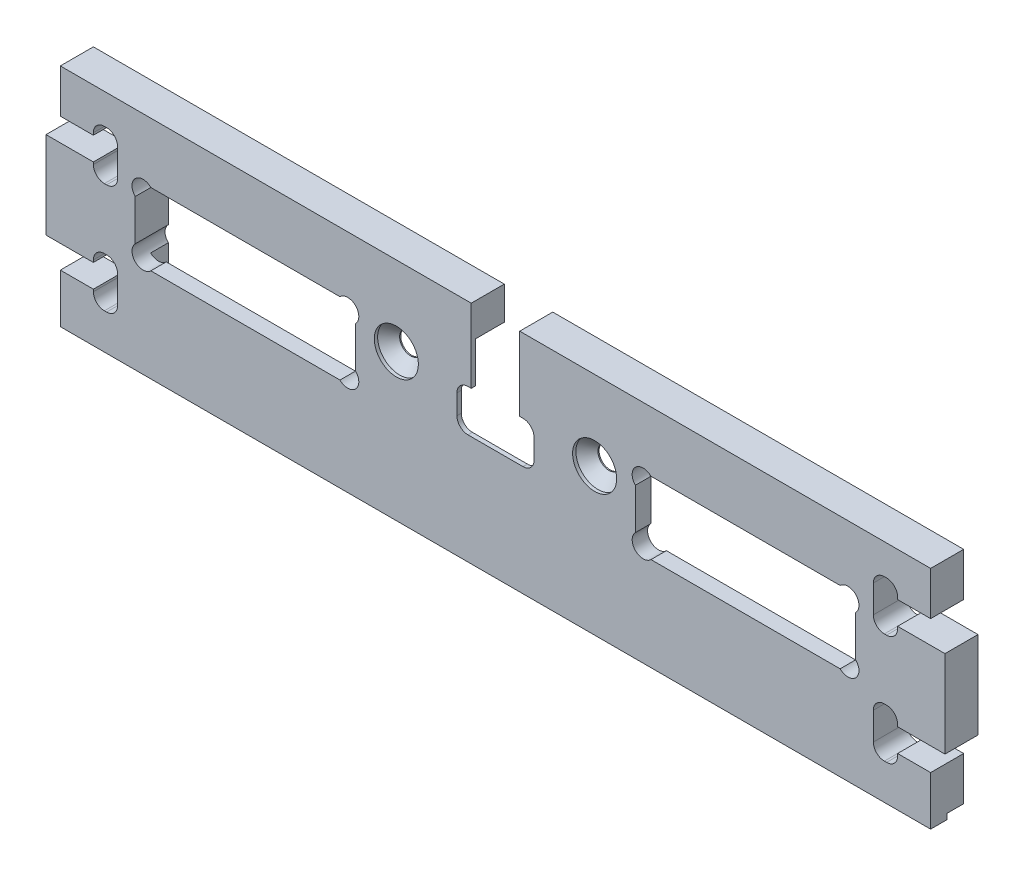
SolidWorks part; units mm, degrees
ref_plane "Front Plane" through (0, 0, 0) normal (0, 0, 1) x (1, 0, 0)
ref_plane "Top Plane" through (0, 0, 0) normal (0, 1, 0) x (1, 0, 0)
ref_plane "Right Plane" through (0, 0, 0) normal (1, 0, 0) x (0, 0, -1)
sketch "Sketch1" plane through (0, 0, 0) normal (0, 0, 1) x (1, 0, 0)
  line L0 (-39.5, 0) -> (39.5, 0) construction
  line L1 (-39.5, 10) -> (39.5, 10)
  line L2 (-39.5, 10) -> (-39.5, -10)
  line L3 (-39.5, -10) -> (39.5, -10)
  line L4 (39.5, 10) -> (39.5, -10)
  line L5 (-39.5, 10) -> (39.5, -10) construction
  line L6 (-39.5, -10) -> (39.5, 10) construction
  line L7 (0, 10) -> (0, -10) construction
  line L9 (-40.8, -3.95) -> (-39.5, -3.95)
  line L10 (-40.8, -3.95) -> (-40.8, 3.95)
  line L11 (-40.8, 3.95) -> (-39.5, 3.95)
  line L12 (-39.5, -3.95) -> (-39.5, 3.95)
  line L13 (-40.8, -3.95) -> (-39.5, 3.95) construction
  line L14 (-40.8, 3.95) -> (-39.5, -3.95) construction
  line L16 (40.8, 3.95) -> (39.5, 3.95)
  line L17 (40.8, -3.95) -> (40.8, 3.95)
  line L18 (40.8, -3.95) -> (39.5, -3.95)
  line L19 (-39.5, 5) -> (39.5, 5) construction
  line L20 (-35.4, 7.25) -> (-35.4, 2.75) construction
  line L21 (-36.5, 3.95) -> (-39.5, 3.95)
  line L22 (-36.5, 3.95) -> (-36.5, 6.05)
  line L23 (-36.5, 6.05) -> (-39.5, 6.05)
  line L24 (-39.5, 3.95) -> (-39.5, 6.05)
  line L25 (-36.5, 3.95) -> (-39.5, 6.05) construction
  line L26 (-36.5, 6.05) -> (-39.5, 3.95) construction
  line L27 (-34.3, 7.25) -> (-36.5, 7.25)
  line L28 (-34.3, 7.25) -> (-34.3, 2.75)
  line L29 (-34.3, 2.75) -> (-36.5, 2.75)
  line L30 (-36.5, 7.25) -> (-36.5, 2.75)
  line L31 (-34.3, 7.25) -> (-36.5, 2.75) construction
  line L32 (-34.3, 2.75) -> (-36.5, 7.25) construction
  line L33 (-34.3, -7.25) -> (-36.5, -7.25)
  line L34 (-34.3, -7.25) -> (-34.3, -2.75)
  line L35 (-34.3, -2.75) -> (-36.5, -2.75)
  line L36 (-36.5, -7.25) -> (-36.5, -2.75)
  line L37 (-36.5, -3.95) -> (-39.5, -3.95)
  line L38 (-36.5, -6.05) -> (-39.5, -6.05)
  line L39 (36.5, 3.95) -> (39.5, 3.95)
  line L40 (36.5, 6.05) -> (39.5, 6.05)
  line L41 (36.5, 7.25) -> (36.5, 2.75)
  line L42 (34.3, 7.25) -> (36.5, 7.25)
  line L43 (34.3, 7.25) -> (34.3, 2.75)
  line L44 (34.3, 2.75) -> (36.5, 2.75)
  line L45 (34.3, -2.75) -> (36.5, -2.75)
  line L46 (34.3, -7.25) -> (34.3, -2.75)
  line L47 (34.3, -7.25) -> (36.5, -7.25)
  line L48 (36.5, -7.25) -> (36.5, -2.75)
  line L49 (36.5, -6.05) -> (39.5, -6.05)
  line L50 (36.5, -3.95) -> (39.5, -3.95)
  point P0 (0, 0)
  point P10 (-40.15, 0)
  point P15 (-38, 5)
  point P35 (-35.4, 5)
  dimension "D1" = 79
  dimension "D2" = 20
  dimension "D4" = 1.3
  dimension "D7" = 5
  dimension "D8" = 2.1
  dimension "D9" = 3
  dimension "D10" = 2.2
  dimension "D11" = 4.5
extrude "Base shape" add sketch "Sketch1" along normal blind 3 contours L4 L1 L2 L3 | L9 L2 L11 L10 | L16 L4 L18 L17 region at (0, 0, 0) region at (-40.15, 0, 0) region at (40.15, 0, 0)
sketch "Sketch4" plane through (0, -10, 0) normal (0, -1, 0) x (1, 0, 0)
  line L0 (39.5, 3) -> (39.5, 0) construction
  line L1 (-39.5, 3) -> (39.5, 3)
  line L2 (-39.5, 3) -> (-39.5, 1.5)
  line L3 (-39.5, 1.5) -> (39.5, 1.5)
  line L4 (39.5, 3) -> (39.5, 1.5)
extrude "Floor lip" add sketch "Sketch4" along normal blind 0.5
sketch "Sketch6" plane through (0, 0, 0) normal (0, 0, -1) x (-1, 0, 0)
  line L0 (0, 0) -> (0, -10) construction
  line L1 (39.5, -10) -> (-39.5, -10) construction
  line L2 (-4, -10) -> (4, -10) construction
  line L3 (39.5, -10) -> (-39.5, -10) construction
  line L4 (-4, -9) -> (4, -9)
  line L5 (-4, -11) -> (4, -11)
  arc A0 (-4, -9) -> (-4, -11) centre (-4, -10) ccw
  arc A1 (4, -11) -> (4, -9) centre (4, -10) ccw
  point P9 (0, -10)
  dimension "D1" = 2
  dimension "D2" = 8
extrude "Nail cutout" cut sketch "Sketch6" against normal up to surface (1.5 mm away) up to face at (0, -10.25, 1.5)
sketch "Sketch3" plane through (-40.8, 0, 0) normal (-1, 0, 0) x (0, 0, 1)
  line L0 (0, 6.05) -> (3, 3.95) construction
  line L1 (0, 6.05) -> (3, 6.05)
  line L2 (0, 6.05) -> (0, 3.95)
  line L3 (0, 3.95) -> (3, 3.95)
  line L4 (3, 6.05) -> (3, 3.95)
  line L5 (0, -3.95) -> (3, -6.05) construction
  line L6 (0, -3.95) -> (3, -3.95)
  line L7 (0, -3.95) -> (0, -6.05)
  line L8 (0, -6.05) -> (3, -6.05)
  line L9 (3, -3.95) -> (3, -6.05)
  point P6 (1.5, 5)
  point P13 (1.5, -5)
ref_axis "Tap axis top" through (-53.7846, 5, 1.5) along (1, 0, 0)
ref_axis "Tap axis bottom" through (-54.2844, -5, 1.5) along (1, 0, 0)
fillet "Mill fillets" radius 1 16 edges at (36.5, -7.25, 1.5) (36.5, 2.75, 1.5) (34.3, 2.75, 1.5) (34.3, -7.25, 1.5) (36.5, -2.75, 1.5) (36.5, 7.25, 1.5) (34.3, -2.75, 1.5) (34.3, 7.25, 1.5) (-36.5, -2.75, 1.5) (-34.3, -2.75, 1.5) (-34.3, -7.25, 1.5) (-36.5, -7.25, 1.5) (-36.5, 2.75, 1.5) (-34.3, 2.75, 1.5) (-34.3, 7.25, 1.5) (-36.5, 7.25, 1.5)
sketch "Sketch8" [suppressed] plane through (0, 0, 3) normal (0, 0, 1) x (1, 0, 0)
  line L0 (-40.8, 0) -> (40.8, 0) construction
  line L1 (-40.8, -3.95) -> (-40.8, 3.95) construction
  line L2 (40.8, -3.95) -> (40.8, 3.95) construction
  line L4 (-24.5, 5.15) -> (24.5, 5.15)
  line L5 (-25.5, 4.15) -> (-25.5, -4.15)
  line L6 (-24.5, -5.15) -> (24.5, -5.15)
  line L7 (25.5, 4.15) -> (25.5, -4.15)
  line L8 (-25.5, 5.15) -> (25.5, -5.15) construction
  line L9 (-25.5, -5.15) -> (25.5, 5.15) construction
  arc A0 (24.5, -5.15) -> (25.5, -4.15) centre (24.5, -4.15) ccw
  arc A1 (24.5, 5.15) -> (25.5, 4.15) centre (24.5, 4.15) cw
  arc A2 (-25.5, -4.15) -> (-24.5, -5.15) centre (-24.5, -4.15) ccw
  arc A3 (-24.5, 5.15) -> (-25.5, 4.15) centre (-24.5, 4.15) ccw
  point P6 (0, 0)
  dimension "D3" = 1
  dimension "D1" = 51
  dimension "D2" = 10.3
extrude "Led strip pocket" [suppressed] cut sketch "Sketch8" against normal offset from surface (2.5 mm away) 0.5 up to face at (0, -0.6712, 0)
sketch "Sketch9" [suppressed] plane through (0, 0, 0.5) normal (0, 0, 1) x (1, 0, 0)
  line L0 (-19.5, 5.15) -> (-19.5, -5.15)
  line L1 (0, 5.15) -> (0, -5.15) construction
  line L2 (19.5, 5.15) -> (19.5, -5.15)
  line L3 (-25.5, -2.978) -> (25.5, -2.978) construction
  line L4 (25.5, -4.15) -> (25.5, 4.15)
  line L5 (24.5, 5.15) -> (-24.5, 5.15)
  line L6 (-25.5, 4.15) -> (-25.5, -4.15)
  line L7 (-24.5, -5.15) -> (24.5, -5.15)
  line L8 (25.5, -4.15) -> (25.5, 4.15)
  line L9 (24.5, 5.15) -> (-24.5, 5.15)
  line L10 (-25.5, 4.15) -> (-25.5, -4.15)
  line L11 (-24.5, -5.15) -> (24.5, -5.15)
  circle A0 centre (-12.7, -2.978) radius 1
  circle A1 centre (12.7, -2.978) radius 1
  arc A4 (24.5, -5.15) -> (25.5, -4.15) centre (24.5, -4.15) ccw
  arc A5 (25.5, 4.15) -> (24.5, 5.15) centre (24.5, 4.15) ccw
  arc A6 (-24.5, 5.15) -> (-25.5, 4.15) centre (-24.5, 4.15) ccw
  arc A7 (-25.5, -4.15) -> (-24.5, -5.15) centre (-24.5, -4.15) ccw
  arc A8 (24.5, -5.15) -> (25.5, -4.15) centre (24.5, -4.15) ccw
  arc A9 (25.5, 4.15) -> (24.5, 5.15) centre (24.5, 4.15) ccw
  arc A10 (-24.5, 5.15) -> (-25.5, 4.15) centre (-24.5, 4.15) ccw
  arc A11 (-25.5, -4.15) -> (-24.5, -5.15) centre (-24.5, -4.15) ccw
  arc M13 (24.5, -5.15) -> (25.5, -4.15) centre (24.5, -4.15) ccw
  line M14 (25.5, -4.15) -> (25.5, 4.15)
  arc M15 (25.5, 4.15) -> (24.5, 5.15) centre (24.5, 4.15) ccw
  line M16 (24.5, 5.15) -> (-24.5, 5.15)
  arc M17 (-24.5, 5.15) -> (-25.5, 4.15) centre (-24.5, 4.15) ccw
  line M18 (-25.5, 4.15) -> (-25.5, -4.15)
  arc M19 (-25.5, -4.15) -> (-24.5, -5.15) centre (-24.5, -4.15) ccw
  line M20 (-24.5, -5.15) -> (24.5, -5.15)
  dimension "D4" = 2
  dimension "D2" = 6
  dimension "D3" = 8.128
  dimension "D5" = 25.4
  dimension "D1" = 0
extrude "Led strip cuts" [suppressed] cut sketch "Sketch9" against normal up to next contours L0 M16 M17 M18 M19 M20 | L2 M16 M20 M13 M14 M15 | A0 | A1
fillet "Led strip cut fillets" [suppressed] radius 1
sketch "Sketch13" plane through (0, 0, 0) normal (0, 0, -1) x (-1, 0, 0)
  line L0 (0, 15.8648) -> (0, -21.9195) construction
  line L2 (-4.2, -6.3) -> (4.2, -6.3)
  line L3 (-5.2, -5.3) -> (-5.2, 6)
  line L4 (-4.2, 7) -> (4.2, 7)
  line L5 (5.2, -5.3) -> (5.2, 6)
  line L6 (-5.2, -6.3) -> (5.2, 7) construction
  line L7 (-5.2, 7) -> (5.2, -6.3) construction
  line L10 (39.5, 10) -> (-39.5, 10) construction
  arc A0 (-4.2, -6.3) -> (-5.2, -5.3) centre (-4.2, -5.3) cw
  arc A1 (4.2, -6.3) -> (5.2, -5.3) centre (4.2, -5.3) ccw
  arc A4 (5.2, 6) -> (4.2, 7) centre (4.2, 6) ccw
  arc A5 (-5.2, 6) -> (-4.2, 7) centre (-4.2, 6) cw
  point P1 (0, 0.35)
  dimension "D4" = 1
  dimension "D5" = 1
  dimension "D1" = 10.4
  dimension "D2" = 13.3
  dimension "D3" = 3
extrude "Bumper mount inner cut" cut sketch "Sketch13" against normal offset from surface (2.6 mm away) 0.4 up to face at (0, -0.0192, 3)
sketch "Sketch14" plane through (0, 0, 0) normal (0, 0, -1) x (-1, 0, 0)
  line L1 (0, 12.9528) -> (0, -14.0841) construction
  line L2 (4.2, 7) -> (-4.2, 7) construction
  line L3 (-4.2, -6.3) -> (4.2, -6.3) construction
  line L4 (-11.7, 7) -> (11.7, 7)
  line L5 (-12.7, 6) -> (-12.7, -5.3)
  line L6 (-11.7, -6.3) -> (11.7, -6.3)
  line L7 (12.7, 6) -> (12.7, -5.3)
  line L8 (-12.7, 7) -> (12.7, -6.3) construction
  line L9 (-12.7, -6.3) -> (12.7, 7) construction
  arc A1 (11.7, -6.3) -> (12.7, -5.3) centre (11.7, -5.3) ccw
  arc A2 (-12.7, -5.3) -> (-11.7, -6.3) centre (-11.7, -5.3) ccw
  arc A3 (11.7, 7) -> (12.7, 6) centre (11.7, 6) cw
  arc A4 (-12.7, 6) -> (-11.7, 7) centre (-11.7, 6) cw
  point P6 (0, 0.35)
  dimension "D2" = 1
  dimension "D3" = 1
  dimension "D1" = 25.4
extrude "Bumper mount outer cut" cut sketch "Sketch14" against normal blind 1.6
sketch "Sketch15" plane through (0, 0, 1.6) normal (0, 0, -1) x (-1, 0, 0)
  line L0 (-12.7, 2.8) -> (12.7, 2.8) construction
  line L3 (0, 16.4744) -> (0, -20.0474) construction
  line L7 (-12.7, 6) -> (-12.7, -5.3) construction
  line L8 (12.7, -5.3) -> (12.7, 6) construction
  line L11 (-4.2, 7) -> (-11.7, 7) construction
  circle A0 centre (-9, 2.8) radius 1
  circle A1 centre (9, 2.8) radius 1
  dimension "D1" = 18
  dimension "D2" = 2
  dimension "D3" = 4.2
extrude "Bumper mount screw holes" cut sketch "Sketch15" against normal up to next
sketch "Sketch16" plane through (0, 0, 2.6) normal (0, 0, -1) x (-1, 0, 0)
  line L0 (-5.2, 1.4) -> (5.2, 1.4) construction
  line L3 (0, 7) -> (0, -4.2) construction
  line L4 (-2.5, 3.3) -> (2.5, 3.3)
  line L5 (-3.5, 2.3) -> (-3.5, 0.5)
  line L6 (-2.5, -0.5) -> (2.5, -0.5)
  line L7 (3.5, 2.3) -> (3.5, 0.5)
  line L8 (-3.5, 3.3) -> (3.5, -0.5) construction
  line L9 (-3.5, -0.5) -> (3.5, 3.3) construction
  line L11 (-5.2, 6) -> (-5.2, -5.3) construction
  line L13 (4.2, 7) -> (-4.2, 7) construction
  arc A0 (2.5, -0.5) -> (3.5, 0.5) centre (2.5, 0.5) ccw
  arc A1 (-3.5, 0.5) -> (-2.5, -0.5) centre (-2.5, 0.5) ccw
  arc A2 (-2.5, 3.3) -> (-3.5, 2.3) centre (-2.5, 2.3) ccw
  arc A3 (2.5, 3.3) -> (3.5, 2.3) centre (2.5, 2.3) cw
  point P6 (0, 1.4)
  dimension "D3" = 1
  dimension "D1" = 7
  dimension "D2" = 3.8
  dimension "D4" = 11.2
extrude "Bumper body cut" cut sketch "Sketch16" against normal up to next
hole_wizard "Bumper screw countersunks" positions "Sketch17" profile "Sketch18" countersink size "M2" standard "ANSI Metric" end condition through all
sketch "Sketch17" plane through (0, 0, 3) normal (0, 0, 1) x (1, 0, 0)
  point P0 (9, 2.8)
  point P3 (-9, 2.8)
sketch "Sketch18" plane through (9, 2.8, 3) normal (1, 0, 0) x (0, -1, 0)
  line L0 (0, 0) -> (0, 3)
  line L1 (0, 3) -> (1, 3)
  line L2 (1, 3) -> (1, 1.3)
  line L3 (1, 1.3) -> (2, 0.3)
  line L4 (2, 0.3) -> (2, 0)
  line L6 (2, 0) -> (0, 0)
  line L7 (-1, 1.3) -> (-2, 0.3) construction
  line L11 (0, -6.35) -> (0, 107.95) construction
  dimension "Thru Hole Dia." = 2
  dimension "Thru Hole Depth" = 3
  dimension "C'Sink Dia." = 4
  dimension "C'Sink Angle" = 90
  dimension "Head Clearance" = 0.3
sketch "Sketch19" plane through (0, 0, 0) normal (0, 0, -1) x (-1, 0, 0)
  line L0 (0, 15.6498) -> (0, -12.9575) construction
  line L1 (39.5, 10) -> (-39.5, 10) construction
  line L2 (-2.2, 3.3) -> (2.2, 3.3)
  line L3 (-2.2, 3.3) -> (-2.2, 10)
  line L4 (-2.2, 10) -> (2.2, 10)
  line L5 (2.2, 3.3) -> (2.2, 10)
  line L6 (-2.2, 3.3) -> (2.2, 10) construction
  line L7 (-2.2, 10) -> (2.2, 3.3) construction
  line L8 (2.5, 3.3) -> (-2.5, 3.3) construction
  point P1 (0, 6.65)
  dimension "D1" = 4.4
extrude "Bumper insertion cut" cut sketch "Sketch19" against normal up to next
sketch "Sketch20" plane through (0, 0, 0) normal (0, 0, -1) x (-1, 0, 0)
  line L0 (-12.7, 6) -> (-12.7, -5.3) construction
  line L1 (-12.7, 4.55) -> (-32.7, 4.55)
  line L2 (-12.7, 4.55) -> (-12.7, -2)
  line L3 (-12.7, -2) -> (-32.7, -2)
  line L4 (-32.7, 4.55) -> (-32.7, -2)
  line L5 (-2.2, 10) -> (-39.5, 10) construction
  line L6 (-12.7, 4.55) -> (-19.25, -2) construction
  line L7 (-22.7, 4.55) -> (-22.7, -2) construction
  line L8 (-32.7, 1.275) -> (-12.7, 1.275) construction
  line L9 (0, 16.176) -> (0, -15.99) construction
  line L10 (12.7, 4.55) -> (12.7, -2)
  line L11 (12.7, -2) -> (32.7, -2)
  line L12 (32.7, 4.55) -> (32.7, -2)
  line L13 (12.7, 4.55) -> (32.7, 4.55)
  circle A0 centre (-13.4071, 3.8429) radius 1
  circle A1 centre (-31.9929, 3.8429) radius 1
  circle A2 centre (-13.4071, -1.2929) radius 1
  circle A3 centre (-31.9929, -1.2929) radius 1
  circle A4 centre (13.4071, 3.8429) radius 1
  circle A5 centre (13.4071, -1.2929) radius 1
  circle A6 centre (31.9929, -1.2929) radius 1
  circle A7 centre (31.9929, 3.8429) radius 1
  dimension "D5" = 2
  dimension "D1" = 20
  dimension "D2" = 5.45
  dimension "D3" = 6.55
  dimension "D4" = 45
extrude "Bumper switches cut" cut sketch "Sketch20" against normal up to next contours L1 L4 L3 L2 | A1 | A3 | A0 | A2 | L13 L12 L11 L10 | A4 | A5 | A6 | A7
sketch "Sketch21" plane through (0, 0, 0) normal (0, 0, -1) x (-1, 0, 0)
  line L0 (-14.1142, -2) -> (-31.2858, -2) construction
  line L1 (-32.7, -2) -> (-12.7, -2)
  line L2 (-32.7, -2) -> (-32.7, -6.3)
  line L3 (-32.7, -6.3) -> (-12.7, -6.3)
  line L4 (-12.7, -2) -> (-12.7, -6.3)
  line L5 (-12.7, -2) -> (-12.7, -5.3) construction
  line L6 (-11.7, -6.3) -> (-4.2, -6.3) construction
  line L7 (-32.7, 3.1358) -> (-32.7, -0.5858) construction
  line L8 (-12.7, -6.3) -> (-11.7, -6.3)
  line L9 (-32.7, -6.3) -> (-28.4, -2) construction
  line L10 (0, 14.2019) -> (0, -15.3745) construction
  line L11 (12.7, -6.3) -> (11.7, -6.3)
  line L12 (12.7, -2) -> (12.7, -6.3)
  line L13 (32.7, -2) -> (12.7, -2)
  line L14 (32.7, -2) -> (32.7, -6.3)
  line L15 (32.7, -6.3) -> (12.7, -6.3)
  arc A0 (-12.7, -5.3) -> (-11.7, -6.3) centre (-11.7, -5.3) ccw construction
  arc A1 (-12.7, -5.3) -> (-11.7, -6.3) centre (-11.7, -5.3) ccw
  circle A2 centre (-31.9929, -5.5929) radius 1
  arc A3 (-32.7, -0.5858) -> (-31.2858, -2) centre (-31.9929, -1.2929) ccw construction
  circle A4 centre (31.9929, -5.5929) radius 1
  arc A5 (12.7, -5.3) -> (11.7, -6.3) centre (11.7, -5.3) cw
  dimension "D1" = 45
extrude "Bumper switch mounts cut" cut sketch "Sketch21" against normal up to surface (1.6 mm away) contours A1 L4 L8 | L12 A5 L11 | L4 L1 L2 L3 | A2 | L12 L13 L14 L15 | A4 region at (12.4766, -6.0766, 0) region at (-12.4766, -6.0766, 0) up to face at (-8, 2.8, 1.6)
sketch "Outer coordinate system sketch" plane through (0, 0, 3) normal (0, 0, 1) x (1, 0, 0)
  line L0 (-35.4, 7.25) -> (-35.4, 2.75) construction
  line L1 (-35.3, 7.25) -> (-35.5, 7.25) construction
  line L2 (-40.8, 3.95) -> (-40.8, 10) construction
  line L3 (-40.8, 10) -> (-39.5, 10) construction
  line L4 (-35.3, 2.75) -> (-35.5, 2.75) construction
  line L5 (0, 15.526) -> (0, -17.3739) construction
  line L6 (-51.2617, 0) -> (56.0692, 0) construction
  circle A0 centre (-35.4, 6.25) radius 1
  point P16 (-35.4, 6.25)
  point P20 (0, 0)
  point P22 (35.4, 6.25)
  point P23 (0, 0)
  point P24 (-35.4, -6.25)
  point P25 (35.4, -6.25)
  dimension "D1" = 2
sketch "Inner coordinate system sketch" plane through (0, 0, 0) normal (0, 0, 1) x (1, 0, 0)
  line L0 (-40.8, -3.95) -> (-40.8, -10) construction
  line L1 (-40.8, -10) -> (-39.5, -10) construction
  line L3 (0, 19.9465) -> (0, -19.5427) construction
  line L4 (53.9633, 0) -> (-51.6097, 0) construction
  point P1 (0, 0)
  point P4 (0, 0)
  point P5 (0, 0)
  point P6 (0, 0)
  point P9 (0, 0)
  point P11 (0, 0)
  point P15 (-39.5, -10)
sketch "Deep inner pocket mill sketch" plane through (0, 0, 2.6) normal (0, 0, -1) x (-1, 0, 0)
  line L0 (-4.2, 7) -> (4.2, 7)
  line L12 (4.2, 7) -> (2.2, 7)
  line L13 (2.2, 7) -> (2.2, 3.3)
  line L14 (2.2, 3.3) -> (2.5, 3.3)
  line L15 (3.5, 2.3) -> (3.5, 0.5)
  line L16 (2.5, -0.5) -> (-2.5, -0.5)
  line L17 (-3.5, 0.5) -> (-3.5, 2.3)
  line L18 (-2.5, 3.3) -> (-2.2, 3.3)
  line L19 (-2.2, 3.3) -> (-2.2, 7)
  line L20 (-2.2, 7) -> (-4.2, 7)
  line L21 (-5.2, 6) -> (-5.2, -5.3)
  line L22 (-4.2, -6.3) -> (4.2, -6.3)
  line L23 (5.2, -5.3) -> (5.2, 6)
  line L33 (-5.2, 6) -> (-5.2, -5.3)
  line L34 (-4.2, -6.3) -> (4.2, -6.3)
  line L35 (5.2, -5.3) -> (5.2, 6)
  arc A8 (3.5, 2.3) -> (2.5, 3.3) centre (2.5, 2.3) ccw
  arc A9 (2.5, -0.5) -> (3.5, 0.5) centre (2.5, 0.5) ccw
  arc A10 (-3.5, 0.5) -> (-2.5, -0.5) centre (-2.5, 0.5) ccw
  arc A11 (-2.5, 3.3) -> (-3.5, 2.3) centre (-2.5, 2.3) ccw
  arc A12 (-4.2, 7) -> (-5.2, 6) centre (-4.2, 6) ccw
  arc A13 (-5.2, -5.3) -> (-4.2, -6.3) centre (-4.2, -5.3) ccw
  arc A14 (4.2, -6.3) -> (5.2, -5.3) centre (4.2, -5.3) ccw
  arc A15 (5.2, 6) -> (4.2, 7) centre (4.2, 6) ccw
  arc A20 (-4.2, 7) -> (-5.2, 6) centre (-4.2, 6) ccw
  arc A21 (-5.2, -5.3) -> (-4.2, -6.3) centre (-4.2, -5.3) ccw
  arc A22 (4.2, -6.3) -> (5.2, -5.3) centre (4.2, -5.3) ccw
  arc A23 (5.2, 6) -> (4.2, 7) centre (4.2, 6) ccw
  dimension "D1" = 0
sketch "Shallow inner pocket mill sketch" plane through (0, 0, 1.6) normal (0, 0, -1) x (-1, 0, 0)
  line L2 (12.7, 4.55) -> (12.7, 6) construction
  line L7 (-12.7, 6) -> (-12.7, 4.55) construction
  line L16 (12.7, 4.55) -> (12.7, 6)
  line L21 (-12.7, 6) -> (-12.7, 4.55)
  line L42 (-32.7, -1) -> (-13.7, -1)
  line L43 (-12.7, 3.1358) -> (-12.7, -0.5858) construction
  line L47 (0, 16.1275) -> (0, -14.7685) construction
  line L53 (-31.2858, -6.3) -> (31.2858, -6.3)
  line L54 (-11.7, 7) -> (11.7, 7)
  line L55 (-12.7, 4.55) -> (-13.7, 4.55)
  line L56 (-13.7, 4.55) -> (-13.7, -1)
  line L58 (-22.7, -2) -> (-22.7, -1) construction
  line L59 (-31.2858, -2) -> (-14.1142, -2) construction
  line L60 (-12.7, 1.275) -> (-13.7, 1.275) construction
  line L61 (-32.7, -1) -> (-32.7, -4.8858)
  line L62 (12.7, 4.55) -> (13.7, 4.55)
  line L63 (13.7, 4.55) -> (13.7, -1)
  line L64 (32.7, -1) -> (13.7, -1)
  line L65 (32.7, -1) -> (32.7, -4.8858)
  arc A2 (12.7, 6) -> (11.7, 7) centre (11.7, 6) ccw construction
  arc A5 (31.2858, -6.3) -> (32.7, -4.8858) centre (31.9929, -5.5929) ccw construction
  arc A10 (-32.7, -4.8858) -> (-31.2858, -6.3) centre (-31.9929, -5.5929) ccw construction
  arc A13 (-11.7, 7) -> (-12.7, 6) centre (-11.7, 6) ccw construction
  arc A16 (12.7, 6) -> (11.7, 7) centre (11.7, 6) ccw
  arc A19 (31.2858, -6.3) -> (32.7, -4.8858) centre (31.9929, -5.5929) ccw
  arc A24 (-32.7, -4.8858) -> (-31.2858, -6.3) centre (-31.9929, -5.5929) ccw
  arc A27 (-11.7, 7) -> (-12.7, 6) centre (-11.7, 6) ccw
  dimension "D1" = 1
